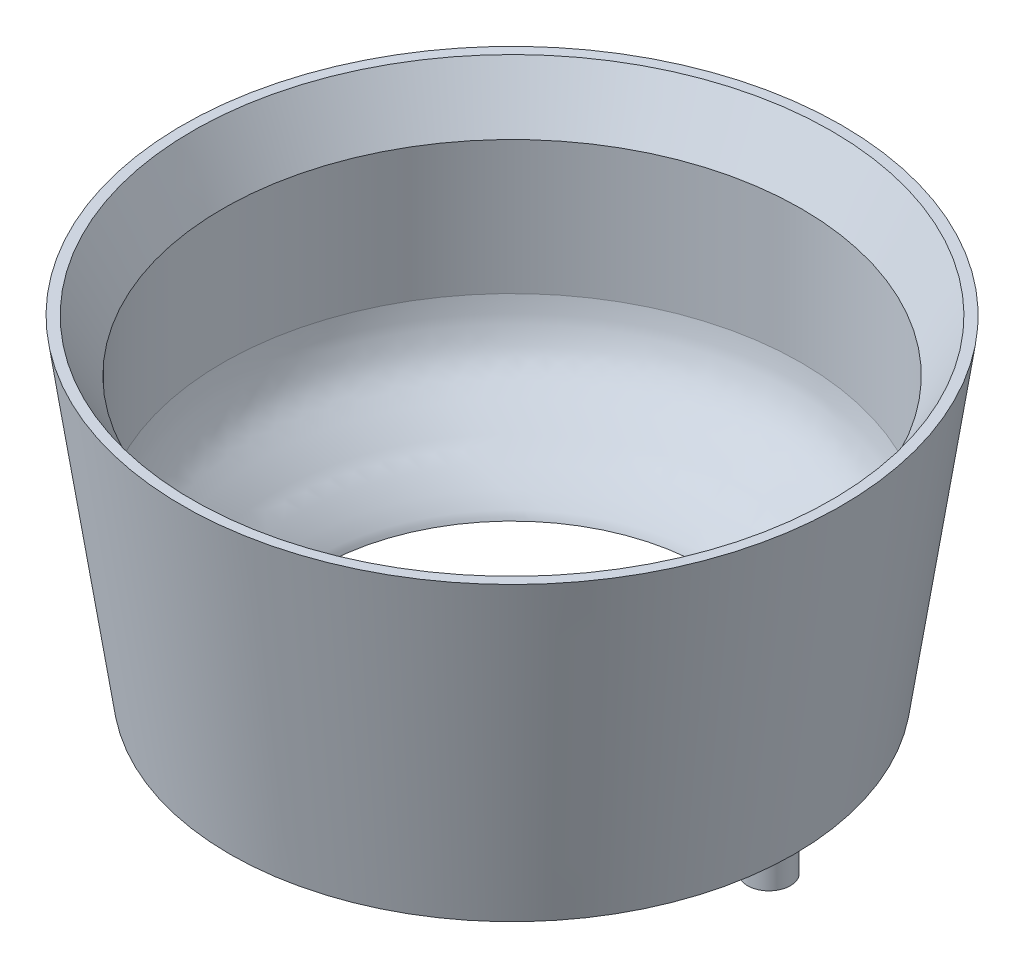
SolidWorks part; units mm, degrees
material "ABS PC"
ref_plane "Front Plane" through (0, 0, 0) normal (0, 0, 1) x (1, 0, 0)
ref_plane "Top Plane" through (0, 0, 0) normal (0, 1, 0) x (1, 0, 0)
ref_plane "Right Plane" through (0, 0, 0) normal (1, 0, 0) x (0, 0, -1)
sketch "Sketch1" plane through (0, 0, 0) normal (1, 0, 0) x (0, 0, -1)
  line L0 (26.0878, 274.978) -> (26.0878, 232.1195)
  line L2 (40.135, 299.274) -> (-40.135, 299.274) construction
  line L5 (0, 324) -> (3.2968, 324)
  line L8 (0, 324) -> (0, 0) construction
  line L9 (26.0878, 262.3641) -> (26.0878, 259.4973) construction
  line L12 (40.135, 302.9291) -> (40.135, 295.6188)
  line L16 (0, 0) -> (51.9362, 327.9125) construction
  line L17 (0, 324) -> (0, 332) construction
  line L18 (26.0878, 274.978) -> (26.0878, 268.978) construction
  line L19 (26.0878, 268.978) -> (26.0878, 248.978) construction
  line L20 (26.0878, 268.978) -> (42.6019, 268.978) construction
  line L21 (26.0878, 274.978) -> (43.5522, 274.978) construction
  line L22 (26.0878, 248.978) -> (39.4342, 248.978) construction
  line L23 (0, 0) -> (-51.9362, 327.9125) construction
  line L24 (-47.4003, 299.274) -> (-47.4003, 268.978) construction
  line L25 (-47.4003, 268.978) -> (-42.6019, 268.978) construction
  line L26 (0, 332) -> (0, 76.96) construction
  line L27 (0, 76.96) -> (400, 76.96) construction
  line L28 (0, 76.96) -> (-400, 76.96) construction
  line L29 (-200, 76.96) -> (-200, 183.96) construction
  line L30 (200, 76.96) -> (200, 183.96) construction
  line L31 (-200, 183.96) -> (-200, 182.57) construction
  line L32 (-200, 182.57) -> (400, 182.57) construction
  line L33 (-200, 182.57) -> (-400, 182.57) construction
  line L38 (0, 186.1152) -> (0, 324)
  line L39 (26.0878, 232.1195) -> (26.0878, 182.57) construction
  line L41 (21.6442, 226.0993) -> (26.0878, 226.0993)
  line L42 (26.0878, 226.0993) -> (26.0878, 186.1152)
  line L43 (26.0878, 186.1152) -> (0, 186.1152)
  line L44 (0, 0) -> (575.122, 0) construction
  arc A0 (-298.7691, 144.7791) -> (305.6579, 129.6043) centre (0, 0) cw construction
  spline S0 degree 3 poles (21.6442, 226.0993) (21.9584, 226.1509) (22.4049, 226.153) (22.896, 226.3321) (23.44, 226.7494) (24.2443, 227.2014) (25.0066, 227.9724) (25.5796, 228.9522) (25.8622, 230.393) (26.0228, 231.4436) (26.0878, 232.1195) knots 0 0 0 0 0.091924 0.112491 0.205673 0.333714 0.459267 0.602423 0.748839 1 1 1 1
  spline S1 degree 3 poles (3.2968, 324) (4.1972, 323.8396) (5.699, 323.816) (7.6935, 323.4297) (9.2722, 323.1563) (10.7507, 322.8538) (12.1816, 322.5577) (13.6372, 322.313) (14.8643, 321.9117) (15.9115, 321.5662) (16.81, 321.2491) (17.7339, 321.0149) (18.8379, 320.6416) (19.931, 320.1935) (21.0686, 319.6948) (22.141, 319.2627) (23.2156, 318.6856) (24.4371, 318.1163) (25.6762, 317.3518) (27.1066, 316.7518) (28.4318, 315.7832) (29.7322, 314.8939) (31.058, 313.93) (32.1959, 312.8581) (33.3378, 311.8503) (34.4539, 310.9646) (35.3895, 309.8867) (36.5078, 309.0949) (37.2942, 308.0208) (38.1233, 307.1238) (38.9048, 306.0961) (39.4724, 304.6349) (40.2774, 303.734) (40.135, 302.9291) knots 0 0 0 0 0.061585 0.100795 0.136831 0.1697 0.202569 0.235438 0.269088 0.289473 0.309858 0.333319 0.353706 0.388423 0.412965 0.437514 0.46634 0.495168 0.528354 0.564387 0.59925 0.638593 0.670824 0.709635 0.743897 0.773612 0.805519 0.839783 0.864953 0.89467 0.922395 0.951224 1 1 1 1
  spline S2 degree 3 poles (40.135, 295.6188) (39.9636, 294.7131) (39.7869, 293.3689) (39.1095, 291.6901) (38.6019, 290.4599) (37.8418, 289.2392) (36.9195, 288.2279) (35.9232, 287.2651) (34.974, 286.2515) (33.8311, 285.3463) (32.8233, 284.2966) (31.8701, 283.2868) (30.7668, 282.4387) (29.8742, 281.4644) (28.8604, 280.5152) (28.0567, 279.5119) (27.1438, 278.5569) (26.4968, 277.0287) (26.0081, 275.8567) (26.0878, 274.978) knots 0 0 0 0 0.108356 0.15601 0.210945 0.263562 0.322855 0.370186 0.4254 0.484692 0.539909 0.595126 0.646549 0.701764 0.749093 0.808384 0.85195 0.901837 1 1 1 1
  point P10 (0, 299.274)
  point P63 (0, 299.274)
  dimension "D3" = 9
  dimension "D1" = 40.135
  dimension "D2" = 324
  dimension "D4" = 8
  dimension "D5" = 3.2968
  dimension "D6" = 4.4435
  dimension "D7" = 6.0202
  dimension "D8" = 7.7403
  dimension "D9" = 6
  dimension "D10" = 20
  dimension "D11" = 9.317
  dimension "D12" = 10.7504
  dimension "D13" = 255.04
  dimension "D14" = 107
  dimension "D15" = 107
  dimension "D16" = 332
  dimension "D17" = 105.61
  dimension "D18" = 105.61
  dimension "D19" = 12.1838
  dimension "D20" = 13.6172
  dimension "D21" = 15.0506
  dimension "D22" = 15.9106
  dimension "D23" = 16.7707
  dimension "D24" = 17.7739
  dimension "D25" = 18.6341
  dimension "D26" = 20.0676
  dimension "D27" = 21.0708
  dimension "D28" = 22.0743
  dimension "D29" = 23.2209
  dimension "D30" = 24.3677
  dimension "D31" = 25.6578
  dimension "D32" = 27.0911
  dimension "D33" = 28.3811
  dimension "D34" = 29.8146
  dimension "D35" = 30.9613
  dimension "D36" = 32.2513
  dimension "D37" = 33.3981
  dimension "D38" = 34.4014
  dimension "D39" = 35.4048
  dimension "D40" = 36.5516
  dimension "D41" = 37.2681
  dimension "D42" = 38.1282
  dimension "D43" = 38.8449
  dimension "D44" = 39.4183
  dimension "D45" = 39.9917
  dimension "D46" = 323.8567
  dimension "D47" = 323.7133
  dimension "D48" = 323.4267
  dimension "D49" = 323.1399
  dimension "D50" = 322.8533
  dimension "D51" = 322.5666
  dimension "D52" = 322.2799
  dimension "D53" = 321.8499
  dimension "D54" = 321.5632
  dimension "D55" = 321.2765
  dimension "D56" = 320.9899
  dimension "D57" = 320.7031
  dimension "D58" = 320.1297
  dimension "D59" = 319.6998
  dimension "D60" = 319.2698
  dimension "D61" = 318.6965
  dimension "D62" = 318.1231
  dimension "D63" = 317.4064
  dimension "D64" = 316.6897
  dimension "D65" = 315.8296
  dimension "D66" = 314.8263
  dimension "D67" = 313.9663
  dimension "D68" = 312.8195
  dimension "D69" = 311.8162
  dimension "D70" = 310.9562
  dimension "D71" = 309.9528
  dimension "D72" = 308.9493
  dimension "D73" = 308.0893
  dimension "D74" = 307.086
  dimension "D75" = 306.0826
  dimension "D76" = 304.9359
  dimension "D77" = 303.9325
  dimension "D78" = 302.9291
sketch "Sketch2" plane through (0, 0, 0) normal (1, 0, 0) x (0, 0, -1)
  line L0 (0, 324) -> (3.2968, 324) construction
  line L1 (26.5078, 274.997) -> (26.5078, 273.8486)
  line L2 (40.5477, 295.5407) -> (40.5477, 314.2386)
  line L3 (40.135, 295.6188) -> (40.135, 302.9302) construction
  line L4 (40.135, 295.6188) -> (26.0878, 274.978) construction
  line L5 (0, 324.42) -> (3.4084, 324.42) construction
  line L6 (3.2968, 324) -> (40.135, 302.9302) construction
  line L7 (3.4084, 324.42) -> (40.555, 303.1738) construction
  line L8 (26.0878, 274.978) -> (26.0878, 232.1195) construction
  line L9 (40.555, 295.4895) -> (26.435, 274.7417) construction
  line L10 (0, 5) -> (0, 407.9498) construction
  line L12 (26.5078, 273.8486) -> (38.5078, 273.8486) construction
  line L13 (26.5078, 274.997) -> (26.5078, 232.1195) construction
  line L14 (38.5078, 273.8486) -> (45.76, 323.5611) construction
  line L17 (40.5477, 314.2386) -> (45.93, 323.5611) construction
  line L18 (45.93, 323.5611) -> (45.76, 323.5611) construction
  line L19 (0, 186.1152) -> (0, 324) construction
  line L20 (0, 324) -> (0, 332) construction
  line L21 (40.555, 295.4895) -> (40.555, 303.1738) construction
  line L22 (0, 5) -> (47.1644, 328.2999) construction
  line L23 (45.93, 323.5611) -> (46.473, 323.5611) construction
  line L24 (46.473, 323.5611) -> (39.2208, 273.8486) construction
  line L25 (39.2208, 273.8486) -> (26.5078, 273.8486)
  line L26 (44.7753, 321.5611) -> (46.1813, 321.5611)
  line L27 (44.7753, 321.5611) -> (40.5477, 314.2386)
  line L28 (46.1813, 321.5611) -> (39.2208, 273.8486)
  spline S0 degree 1 poles (40.5477, 295.5407) (26.5078, 274.997) knots 0 0 1 1 construction
  spline S1 degree 3 poles (40.135, 295.6188) (39.9636, 294.7131) (39.7869, 293.3689) (39.1095, 291.6901) (38.6019, 290.4599) (37.8418, 289.2392) (36.9195, 288.2279) (35.9232, 287.2651) (34.974, 286.2515) (33.8311, 285.3463) (32.8233, 284.2966) (31.8701, 283.2868) (30.7668, 282.4387) (29.8742, 281.4644) (28.8604, 280.5152) (28.0567, 279.5119) (27.1438, 278.5569) (26.4968, 277.0287) (26.0081, 275.8567) (26.0878, 274.978) knots 0 0 0 0 0.108356 0.15601 0.210945 0.263562 0.322855 0.370186 0.4254 0.484692 0.539909 0.595126 0.646549 0.701764 0.749093 0.808384 0.85195 0.901837 1 1 1 1 construction
  spline S2 degree 3 poles (40.5477, 295.5407) (40.4477, 295.0127) (40.2928, 293.9708) (39.9309, 292.5875) (39.5162, 291.5815) (39.1084, 290.578) (38.4397, 289.317) (37.3314, 288.0326) (36.3684, 287.1154) (35.6302, 286.3401) (35.0165, 285.7627) (34.3943, 285.2472) (33.6355, 284.5566) (32.9204, 283.7714) (32.1297, 282.9861) (31.4852, 282.4595) (30.915, 281.9635) (30.3717, 281.3913) (29.7828, 280.8046) (29.2276, 280.2622) (28.7248, 279.6749) (28.1804, 279.0397) (27.6518, 278.4702) (27.3081, 277.8768) (26.9952, 277.1272) (26.598, 276.1645) (26.4648, 275.4705) (26.5078, 274.997) knots 0 0 0 0 0.062544 0.125088 0.15636 0.187632 0.250176 0.31272 0.375264 0.406536 0.437808 0.46908 0.500352 0.562896 0.594168 0.62544 0.656713 0.687985 0.719257 0.750529 0.781801 0.813073 0.844345 0.875617 0.906889 0.938161 1.000705 1.000705 1.000705 1.000705
  point P38 (0, 328)
  dimension "D4" = 1.1484
  dimension "D5" = 8.3
  dimension "D6" = 30
  dimension "D7" = 45.93
  dimension "D8" = 40.39
  dimension "D9" = 8.3
  dimension "D10" = 40.5477
  dimension "D3" = 12
  dimension "D11" = 18.6979
  dimension "D12" = 2
  dimension "D13" = 5
  dimension "D1" = 0.42
  dimension "D2" = 0.42
revolve "Revolve6" add sketch "Sketch2" angle 360 about L10
sketch "Sketch3" plane through (0, 0, 0) normal (1, 0, 0) x (0, 0, -1)
  line L0 (44.1979, 321.5611) -> (40.5477, 314.2386) construction
  line L3 (46.1813, 321.5611) -> (-46.1813, 321.5611) construction
  line L4 (44.7753, 321.5611) -> (-44.7753, 321.5611) construction
  line L5 (40.5477, 314.2386) -> (-40.5477, 314.2386) construction
  line L6 (40.5477, 314.2386) -> (54.812, 333.8718)
  line L8 (54.812, 333.8718) -> (54.812, 347.837)
  line L9 (54.812, 347.837) -> (0, 347.837)
  line L10 (0, 347.837) -> (0, 311.6751)
  line L11 (0, 186.1152) -> (0, 324) construction
  line L12 (0, 311.6751) -> (40.5477, 311.6751)
  line L13 (40.5477, 311.6751) -> (40.5477, 314.2386)
  dimension "D1" = 36
  dimension "D2" = 54.812
revolve "Cut-Revolve1" [suppressed] cut sketch "Sketch3" angle 360 about L10
sketch "Sketch4" plane through (0, 273.8486, 0) normal (0, -1, 0) x (1, 0, 0)
  line L0 (0, 0) -> (36, 0) construction
  line L1 (0, 0) -> (-31.1769, 18) construction
  circle A0 centre (0, 0) radius 36 construction
  circle A1 centre (-31.1769, 18) radius 3
  circle A2 centre (36, 0) radius 3
  dimension "D1" = 72
  dimension "D3" = 6
  dimension "D4" = 6
  dimension "D2" = 150
extrude "Boss-Extrude1" add sketch "Sketch4" along normal blind 2
sketch "Sketch5" [suppressed] plane through (0, 263.8486, 0) normal (0, -1, 0) x (1, 0, 0)
  circle A0 centre (36, 0) radius 3.175
  circle A1 centre (-31.1769, 18) radius 3.175
  dimension "D1" = 6.35
  dimension "D2" = 6.35
extrude "Boss-Extrude2" [suppressed] add sketch "Sketch5" along normal blind 5
chamfer "Chamfer2" [suppressed] distance 9 angle 4
sketch "Sketch7" plane through (0, 0, 0) normal (1, 0, 0) x (0, 0, -1)
  line L0 (0, 5) -> (0, 407.9498) construction
  line L1 (26.5078, 273.8486) -> (39.2208, 273.8486) construction
  line L2 (39.2208, 273.8486) -> (39.2208, 272.3194)
  line L4 (26.5078, 273.8486) -> (26.5078, 274.3486)
  line L5 (26.5078, 274.3486) -> (39.2208, 274.3486)
  line L6 (39.2208, 274.3486) -> (39.2208, 273.8486)
  circle A0 centre (0, -0.122) radius 275.25 construction
  arc A1 (39.2208, 272.3194) -> (26.5078, 273.8486) centre (0, -0.122) ccw
  dimension "D1" = 550.5
  dimension "D2" = 0.5
revolve "Revolve7" add sketch "Sketch7" angle 360 about L10
sketch "Sketch12" plane through (0, 0, 0) normal (1, 0, 0) x (0, 0, -1)
  line L0 (26.5078, 273.8486) -> (26.5078, 277.4868) construction
  line L1 (26.0878, 277.5266) -> (26.0878, 267.5266)
  line L2 (26.0878, 274.978) -> (26.0878, 232.1195) construction
  line L3 (26.0878, 267.5266) -> (40.0878, 267.5266)
  line L4 (40.0878, 267.5266) -> (40.0878, 275.8524)
  line L5 (0, 0) -> (0, 301.1246) construction
  line L6 (0, 5) -> (0, 407.9498) construction
  circle A0 centre (0, 0) radius 278.75 construction
  arc A1 (40.0878, 275.8524) -> (26.0878, 277.5266) centre (0, 0) ccw
  dimension "D1" = 557.5
  dimension "D2" = 10
  dimension "D3" = 14
revolve "Cut-Revolve3" cut sketch "Sketch12" angle 360 about L10
extrude "Boss-Extrude3" add sketch "Sketch4<2>" along normal blind 2 and the other way up to next
sketch "Sketch4<2>" plane through (0, 273.8486, 0) normal (0, -1, 0) x (1, 0, 0) same geometry as "Sketch4"
sketch "Sketch13" plane through (0, 271.8486, 0) normal (0, -1, 0) x (1, 0, 0)
  circle A0 centre (-31.1769, 18) radius 1.5
  circle A1 centre (36, 0) radius 1.5
  dimension "D1" = 3
  dimension "D2" = 3
extrude "Cut-Extrude1" cut sketch "Sketch13" against normal blind 6
sketch "Sketch14" plane through (0, 271.8486, 0) normal (0, -1, 0) x (1, 0, 0)
  circle A0 centre (-31.1769, 18) radius 2
  circle A1 centre (36, 0) radius 2
  dimension "D1" = 4
  dimension "D2" = 4
extrude "Cut-Extrude2" cut sketch "Sketch14" against normal blind 0.5
chamfer "Chamfer3" distance 0.55 angle 45 2 edges at (36, 271.8486, -2) (-31.1769, 271.8486, 16)
